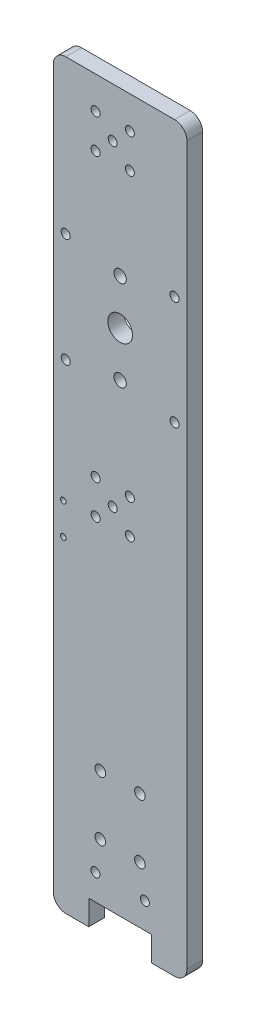
SolidWorks part; units mm, degrees
ref_plane "Front Plane" through (0, 0, 0) normal (0, 0, 1) x (1, 0, 0)
ref_plane "Top Plane" through (0, 0, 0) normal (0, 1, 0) x (1, 0, 0)
ref_plane "Right Plane" through (0, 0, 0) normal (1, 0, 0) x (0, 0, -1)
sketch "Sketch1" plane through (0, 0, 0) normal (0, 0, 1) x (1, 0, 0)
  line L0 (-27, -150) -> (-27, 150)
  line L1 (-27, -150) -> (27, -150)
  line L2 (-27, 150) -> (27, 150)
  line L3 (27, -150) -> (27, 150)
  line L4 (-27, -150) -> (27, 150) construction
  line L5 (-27, 150) -> (27, -150) construction
  point P1 (0, 0)
  dimension "D1" = 54
  dimension "D2" = 300
extrude "Boss-Extrude1" add sketch "Sketch1" along normal blind 6.35
fillet "Fillet1" radius 5 4 edges at (27, -150, 3.175) (-27, -150, 3.175) (27, 150, 3.175) (-27, 150, 3.175)
sketch "Sketch2" plane through (0, 0, 6.35) normal (0, 0, 1) x (1, 0, 0)
  line L0 (-3, 130) -> (-3, 1.948) construction
  line L1 (22, 150) -> (-22, 150) construction
  line L2 (-9.9148, 123.0852) -> (-9.9148, 136.9148) construction
  line L3 (-9.9148, 123.0852) -> (3.9148, 123.0852) construction
  line L4 (-9.9148, 136.9148) -> (3.9148, 136.9148) construction
  line L5 (3.9148, 123.0852) -> (3.9148, 136.9148) construction
  line L6 (-9.9148, 123.0852) -> (3.9148, 136.9148) construction
  line L7 (-9.9148, 136.9148) -> (3.9148, 123.0852) construction
  line L8 (-9.9148, -4.9668) -> (-9.9148, 8.8628) construction
  line L9 (-9.9148, -4.9668) -> (3.9148, -4.9668) construction
  line L10 (-9.9148, 8.8628) -> (3.9148, 8.8628) construction
  line L11 (3.9148, -4.9668) -> (3.9148, 8.8628) construction
  line L12 (-9.9148, -4.9668) -> (3.9148, 8.8628) construction
  line L13 (-9.9148, 8.8628) -> (3.9148, -4.9668) construction
  line L14 (-22, 43.974) -> (-22, 87.974) construction
  line L15 (-22, 43.974) -> (22, 43.974) construction
  line L16 (-22, 87.974) -> (22, 87.974) construction
  line L17 (22, 43.974) -> (22, 87.974) construction
  line L18 (-22, 43.974) -> (22, 87.974) construction
  line L19 (-22, 87.974) -> (22, 43.974) construction
  line L20 (0, 47.724) -> (0, 84.224) construction
  point P2 (-3, 65.974)
  point P3 (0, 65.974)
  point P7 (0, 65.974)
  point P22 (0, 65.974)
  dimension "D1" = 128.052
  dimension "D2" = 20
  dimension "D3" = 19.558
  dimension "D4" = 44
  dimension "D5" = 36.5
  dimension "D6" = 3
sketch "Sketch3" plane through (0, 0, 6.35) normal (0, 0, 1) x (1, 0, 0)
  circle A0 centre (0, 65.974) radius 5
  dimension "D1" = 10
extrude "Cut-Extrude1" cut sketch "Sketch3" against normal through all
hole_wizard "#6 Clearance Hole1" positions "Sketch5" profile "Sketch4" hole size "#6" standard "ANSI Inch" end condition through all
sketch "Sketch5" plane through (0, 0, 6.35) normal (0, 0, 1) x (1, 0, 0)
  point P0 (-22, 87.974)
  point P3 (-22, 43.974)
  point P6 (22, 43.974)
  point P9 (22, 87.974)
  point P12 (-9.9148, 123.0852)
  point P15 (-9.9148, 136.9148)
  point P18 (3.9148, 136.9148)
  point P21 (3.9148, 123.0852)
  point P24 (-9.9148, 8.8628)
  point P27 (3.9148, 8.8628)
  point P30 (3.9148, -4.9668)
  point P33 (-9.9148, -4.9668)
  point P36 (-3, 130)
  point P39 (-3, 1.948)
sketch "Sketch4" plane through (-22, 87.974, 6.35) normal (1, 0, 0) x (0, -1, 0)
  line L0 (0, 0) -> (0, 6.35)
  line L1 (0, 6.35) -> (1.8288, 6.35)
  line L2 (1.8288, 6.35) -> (1.8288, 0)
  line L5 (1.8288, 0) -> (0, 0)
  line L11 (0, -6.35) -> (0, 107.95) construction
  dimension "Thru Hole Dia." = 3.6576
  dimension "Thru Hole Depth" = 6.35
sketch "Sketch6" plane through (0, 0, 6.35) normal (0, 0, 1) x (1, 0, 0)
  line L0 (-12.7, -150) -> (-12.6, -140)
  line L1 (-22, -150) -> (22, -150) construction
  line L2 (-12.6, -140) -> (12.6, -140)
  line L3 (12.6, -140) -> (12.7, -150)
  line L4 (12.7, -150) -> (-12.7, -150)
  point P4 (0, -140)
  point P7 (0, -150)
  dimension "D1" = 10
  dimension "D2" = 25.2
  dimension "D3" = 25.4
extrude "Cut-Extrude2" cut sketch "Sketch6" against normal through all
hole_wizard "#10 Clearance Hole2" positions "Sketch10" profile "Sketch9" hole size "#10" standard "ANSI Inch" end condition through all
sketch "Sketch10" plane through (0, 0, 6.35) normal (0, 0, 1) x (1, 0, 0)
  point P0 (0, 47.724)
  point P3 (0, 84.224)
sketch "Sketch9" plane through (0, 47.724, 6.35) normal (1, 0, 0) x (0, -1, 0)
  line L0 (0, 0) -> (0, 6.35)
  line L1 (0, 6.35) -> (2.4892, 6.35)
  line L2 (2.4892, 6.35) -> (2.4892, 0)
  line L5 (2.4892, 0) -> (0, 0)
  line L11 (0, -6.35) -> (0, 107.95) construction
  dimension "Thru Hole Dia." = 4.9784
  dimension "Thru Hole Depth" = 6.35
sketch "Sketch11" plane through (0, 0, 6.35) normal (0, 0, 1) x (1, 0, 0)
  line L0 (-10, -129.5352) -> (10, -129.5352) construction
  line L1 (12.6, -140) -> (-12.6, -140) construction
  point P2 (0, -129.5352)
  dimension "D1" = 20
  dimension "D2" = 10.4648
hole_wizard "#6 Clearance Hole2" positions "3DSketch1" profile "Sketch12" hole size "#6" standard "ANSI Inch" end condition through all
sketch3d "3DSketch1"
  point P0 (-10, -129.5352, 6.35)
  point P3 (10, -129.5352, 6.35)
sketch "Sketch12" plane through (-10, -129.5352, 6.35) normal (1, 0, 0) x (0, -1, 0)
  line L0 (0, 0) -> (0, 6.35)
  line L1 (0, 6.35) -> (1.8288, 6.35)
  line L2 (1.8288, 6.35) -> (1.8288, 0)
  line L5 (1.8288, 0) -> (0, 0)
  line L11 (0, -6.35) -> (0, 107.95) construction
  dimension "Thru Hole Dia." = 3.6576
  dimension "Thru Hole Depth" = 6.35
sketch "Sketch13" plane through (0, 0, 6.35) normal (0, 0, 1) x (1, 0, 0)
  line L0 (12.6, -140) -> (-12.6, -140) construction
  line L1 (-8, -93) -> (8, -93) construction
  line L2 (-8, -93) -> (-8, -117) construction
  line L3 (-8, -117) -> (8, -117) construction
  line L4 (8, -93) -> (8, -117) construction
  line L5 (-8, -93) -> (8, -117) construction
  line L6 (-8, -117) -> (8, -93) construction
  point P0 (0, -105)
  dimension "D1" = 16
  dimension "D2" = 24
  dimension "D3" = 35
hole_wizard "#8 Clearance Hole1" positions "3DSketch2" profile "Sketch14" hole size "#8" standard "ANSI Inch" end condition through all
sketch3d "3DSketch2"
  point P0 (-8, -93, 6.35)
  point P3 (8, -93, 6.35)
  point P6 (8, -117, 6.35)
  point P9 (-8, -117, 6.35)
sketch "Sketch14" plane through (-8, -93, 6.35) normal (1, 0, 0) x (0, -1, 0)
  line L0 (0, 0) -> (0, 6.35)
  line L1 (0, 6.35) -> (2.1526, 6.35)
  line L2 (2.1526, 6.35) -> (2.1526, 0)
  line L5 (2.1526, 0) -> (0, 0)
  line L11 (0, -6.35) -> (0, 107.95) construction
  dimension "Thru Hole Dia." = 4.3053
  dimension "Thru Hole Depth" = 6.35
sketch "Sketch15" plane through (0, 0, 6.35) normal (0, 0, 1) x (1, 0, 0)
  line L0 (-23, -5.926) -> (-23, -18.626) construction
  point P2 (-3, 1.948)
  point P3 (-23, -9.8538)
  point P5 (0, 0)
  point P6 (0, 0)
  point P7 (0, 0)
  point P8 (-23, -12.276)
  dimension "D1" = 12.7
  dimension "D2" = 20
  dimension "D3" = 14.224
hole_wizard "Tap Drill for #4-40 Tap1" positions "3DSketch3" profile "Sketch16" hole size "#4-40" standard "ANSI Inch"
sketch3d "3DSketch3"
  point P0 (-23, -18.626, 6.35)
  point P3 (-23, -5.926, 6.35)
sketch "Sketch16" plane through (-23, -18.626, 6.35) normal (1, 0, 0) x (0, -1, 0)
  line L0 (0, 0) -> (0, 7.0292)
  line L1 (0, 7.0292) -> (1.1303, 6.35)
  line L2 (1.1303, 6.35) -> (1.1303, 0)
  line L5 (1.1303, 0) -> (0, 0)
  line L10 (0, 7.0292) -> (-1.1303, 6.35) construction
  line L11 (0, -6.35) -> (0, 107.95) construction
  dimension "Hole Dia." = 2.2606
  dimension "Hole Depth" = 6.35
  dimension "Drill Angle" = 118
